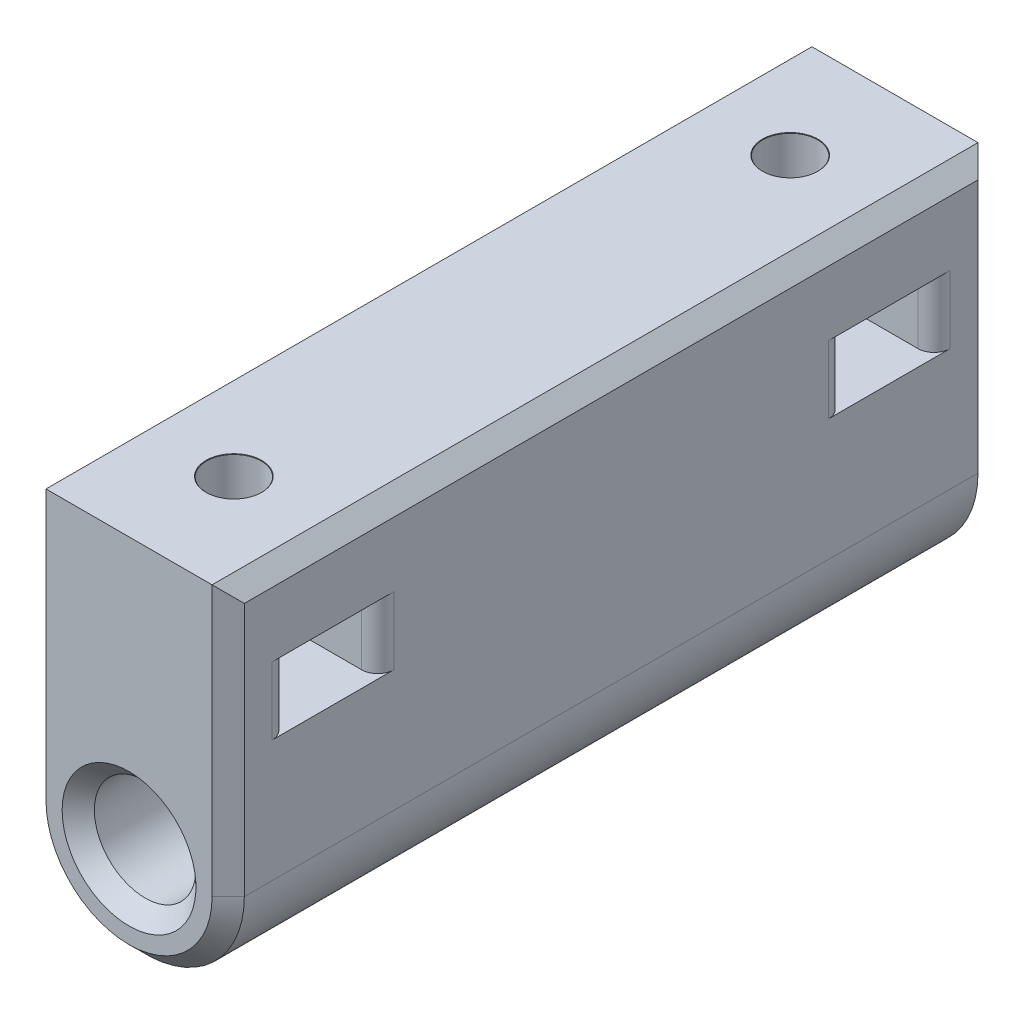
SolidWorks part; units mm, degrees
material "Hollow 3D Print"
ref_plane "Front Plane" through (0, 0, 0) normal (0, 0, 1) x (1, 0, 0)
ref_plane "Top Plane" through (0, 0, 0) normal (0, 1, 0) x (1, 0, 0)
ref_plane "Right Plane" through (0, 0, 0) normal (1, 0, 0) x (0, 0, -1)
sketch "Sketch1" plane through (0, 0, 0) normal (0, 0, 1) x (1, 0, 0)
  line L0 (0, 0) -> (0, 16.75) construction
  line L1 (6.15, 0) -> (6.15, 16.75)
  line L2 (-6.15, 0) -> (-6.15, 16.75)
  line L3 (-6.15, 16.75) -> (6.15, 16.75)
  circle A0 centre (0, 0) radius 3.15
  arc A1 (6.15, 0) -> (-6.15, 0) centre (0, 0) cw
  point P4 (0, 0)
  dimension "D2" = 3
  dimension "D3" = 6.3
  dimension "D1" = 16.75
extrude "Boss-Extrude1" add sketch "Sketch1" along normal blind 47.5
sketch "Sketch3" plane through (6.15, 0, 0) normal (1, 0, 0) x (0, 0, -1)
  line L1 (-47.5, 16.75) -> (0, 16.75) construction
  line L2 (-25.85, 6.15) -> (-21.65, 6.15)
  line L4 (-23.75, 6.15) -> (-23.75, 16.75) construction
  line L6 (-47.5, 0) -> (0, 0) construction
  line L7 (0, -6.15) -> (0, 0) construction
  line L8 (0, -6.15) -> (0, 0) construction
  line L9 (-23.75, 6.15) -> (-23.75, 0) construction
  point P8 (-23.75, 0)
ref_plane "Plane1" through (0, 11.75, 0) normal (0, 1, 0) x (1, 0, 0)
sketch "Sketch4" plane through (0, 11.75, 0) normal (0, 1, 0) x (1, 0, 0)
  line L0 (6.15, -47.5) -> (-6.15, -47.5) construction
  line L1 (-3.2043, -41) -> (-1.6021, -43.775)
  line L2 (-1.6021, -43.775) -> (1.6021, -43.775)
  line L3 (1.6021, -43.775) -> (3.2043, -41) construction
  line L4 (3.2043, -41) -> (1.6021, -38.225) construction
  line L5 (1.6021, -38.225) -> (-1.6021, -38.225)
  line L6 (-1.6021, -38.225) -> (-3.2043, -41)
  line L7 (6.15, -47.5) -> (-6.15, -47.5)
  line L8 (0, -47.5) -> (0, -41) construction
  line L9 (1.6021, -38.225) -> (6.15, -38.225)
  line L10 (6.15, -38.225) -> (6.15, -43.775)
  line L11 (6.15, -43.775) -> (1.6021, -43.775)
  circle A0 centre (0, -41) radius 2.775 construction
  point P11 (0, 0)
  point P14 (0, 0)
  dimension "D1" = 5.55
  dimension "D2" = 6.5
extrude "Cut-Extrude1" cut sketch "Sketch4" against normal blind 4.2 contours L11 L2 L1 L6 L5 L9 L10
ref_plane "Plane2" through (0, 0, 23.75) normal (0, 0, -1) x (-1, 0, 0)
sketch "Sketch6" plane through (0, 16.75, 0) normal (0, 1, 0) x (1, 0, 0)
  point P0 (0, -41)
hole_wizard "M3 Clearance Hole1" positions "Sketch6" profile "Sketch7" hole size "M3" standard "ANSI Metric"
sketch "Sketch7" plane through (0, 16.75, 41) normal (1, 0, 0) x (0, 0, 1)
  line L0 (0, 0) -> (0, 17.7705)
  line L1 (0, 17.7705) -> (1.7, 16.749)
  line L2 (1.7, 16.749) -> (1.7, 0.025)
  line L3 (1.7, 0.025) -> (1.725, 0)
  line L5 (1.725, 0) -> (0, 0)
  line L6 (-1.7, 0.025) -> (-1.725, 0) construction
  line L10 (0, 17.7705) -> (-1.7, 16.749) construction
  line L11 (0, -6.35) -> (0, 107.95) construction
  dimension "Hole Dia." = 3.4
  dimension "Hole Depth" = 16.749
  dimension "Near C'Sink Dia." = 3.45
  dimension "Near C'Sink Angle" = 90
  dimension "Drill Angle" = 118
mirror "Mirror1" about plane through (0, 0, 23.75) normal (0, 0, -1) of "M3 Clearance Hole1", "Cut-Extrude1"
fillet "Fillet1" radius 1 4 edges at (6.15, 9.65, 9.275) (6.15, 9.65, 3.725) (6.15, 9.65, 43.775) (6.15, 9.65, 38.225)
chamfer "Chamfer1" distance 1 angle 45 8 edges at (-6.15, 16.75, 23.75) (-6.15, 8.375, 0) (-6.15, 8.375, 47.5) (0, -6.15, 0) (0, -6.15, 47.5) (6.15, 8.375, 0) (6.15, 16.75, 23.75) (6.15, 8.375, 47.5)
chamfer "Chamfer2" distance 1 angle 45 2 edges at (3.15, 0, 0) (3.15, 0, 47.5)
